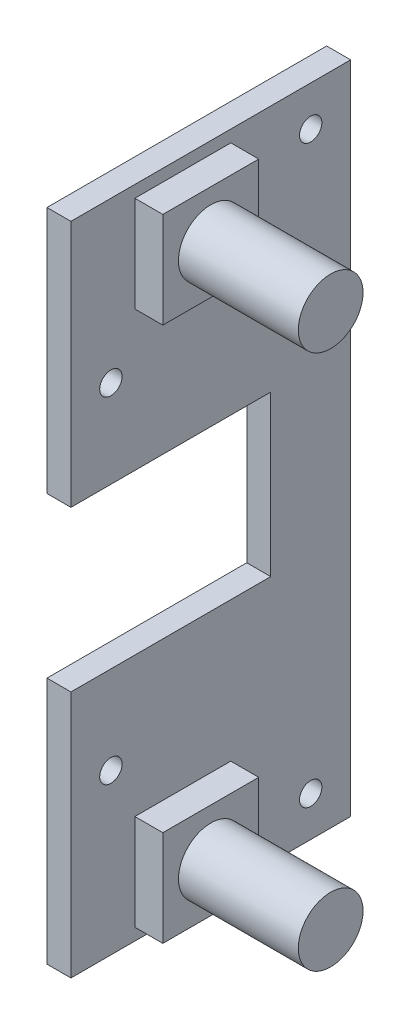
SolidWorks part; units mm, degrees
ref_plane "前基準面" through (0, 0, 0) normal (0, 0, 1) x (1, 0, 0)
ref_plane "上基準面" through (0, 0, 0) normal (0, 1, 0) x (1, 0, 0)
ref_plane "右基準面" through (0, 0, 0) normal (1, 0, 0) x (0, 0, -1)
ref_axis "基準軸1" through (0, -55, 0) along (0, 1, 0)
ref_axis "基準軸2" through (-88.99, 0, 0) along (1, 0, 0)
ref_axis "基準軸3" through (0, 0, 55) along (0, 0, -1)
sketch "草圖1" plane through (0, 0, 0) normal (1, 0, 0) x (0, 0, -1)
  line L0 (-35, -10) -> (-35, -41)
  line L1 (-35, -41) -> (0, -41)
  line L2 (0, -41) -> (0, 41)
  line L3 (0, 41) -> (-35, 41)
  line L4 (-35, 41) -> (-35, 10)
  line L5 (-35, 10) -> (-10, 10)
  line L6 (-10, 10) -> (-10, -10)
  line L7 (-10, -10) -> (-35, -10)
  line L8 (19.25, 0) -> (-19.25, 0) construction
  line L9 (0, 45.1) -> (0, -45.1) construction
  point P10 (0, 0)
  dimension "D1" = 31
  dimension "D2" = 31
  dimension "D3" = 82
  dimension "D4" = 35
  dimension "D5" = 35
  dimension "D6" = 25
  dimension "D7" = 0
extrude "填料-伸長1" add sketch "草圖1" along normal blind 3
sketch "草圖2" plane through (3, 0, 0) normal (1, 0, 0) x (0, 0, -1)
  line L1 (-27, -39.5) -> (-15, -39.5)
  line L2 (-27, -39.5) -> (-27, -27.5)
  line L3 (-27, -27.5) -> (-15, -27.5)
  line L4 (-15, -39.5) -> (-15, -27.5)
  line L7 (-35, -10) -> (-35, -41) construction
  line L8 (-35, -41) -> (0, -41) construction
  point P4 (-21, -27.5)
  point P7 (-15, -33.5)
  dimension "D1" = 12
  dimension "D2" = 12
  dimension "D3" = 14
  dimension "D4" = 7.5
extrude "填料-伸長2" add sketch "草圖2" along normal blind 3.5
sketch "草圖3" plane through (6.5, 0, 0) normal (1, 0, 0) x (0, 0, -1)
  line L0 (-35, -41) -> (0, -41) construction
  line L1 (-35, -10) -> (-35, -41) construction
  circle A0 centre (-21, -33.5) radius 4.05
  dimension "D1" = 8.1
  dimension "D2" = 7.5
  dimension "D3" = 14
extrude "填料-伸長3" add sketch "草圖3" along normal blind 15
ref_plane "平面1" through (14, 0, 0) normal (1, 0, 0) x (0, 0, -1)
mirror "鏡射1" about plane through (0, 0, 0) normal (0, 1, 0) of "填料-伸長3", "填料-伸長2"
sketch "草圖4" plane through (3, 0, 0) normal (1, 0, 0) x (0, 0, -1)
  line L0 (-35, -10) -> (-35, -41) construction
  line L1 (-35, -41) -> (0, -41) construction
  line L2 (0, -41) -> (0, 41) construction
  circle A0 centre (-30, -21) radius 1.4
  circle A1 centre (-5, -36) radius 1.4
  dimension "D1" = 2.8
  dimension "D4" = 2.8
  dimension "D2" = 5
  dimension "D3" = 20
  dimension "D5" = 5
  dimension "D6" = 5
extrude "除料-伸長1" cut sketch "草圖4" against normal up to next
mirror "鏡射2" about plane through (0, 0, 0) normal (0, 1, 0) of "除料-伸長1"
